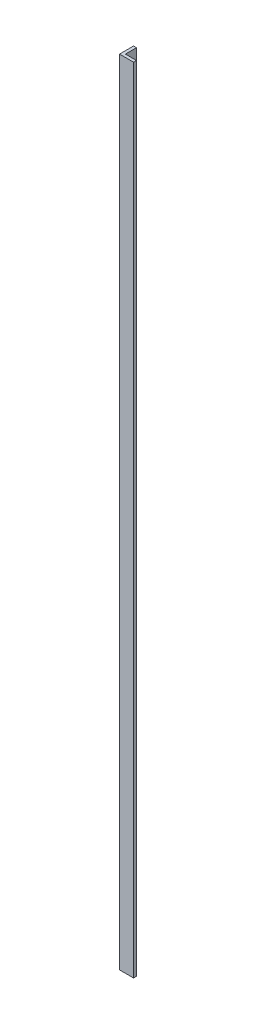
SolidWorks part; units mm, degrees
material "PE Low/Medium Density"
ref_plane "Front Plane" through (0, 0, 0) normal (0, 0, 1) x (1, 0, 0)
ref_plane "Top Plane" through (0, 0, 0) normal (0, 1, 0) x (1, 0, 0)
ref_plane "Right Plane" through (0, 0, 0) normal (1, 0, 0) x (0, 0, -1)
sketch "Sketch1" plane through (0, 0, 0) normal (0, 1, 0) x (1, 0, 0)
  line L1 (0, 0) -> (7.5875, 0)
  line L2 (0, 0) -> (0, 7.5875)
  line L3 (0, 7.5875) -> (1.5875, 7.5875)
  line L4 (7.5875, 0) -> (7.5875, 1.5875)
  line L7 (7.5875, 1.5875) -> (1.5875, 1.5875)
  line L8 (1.5875, 7.5875) -> (1.5875, 1.5875)
  dimension "D1" = 7.5875
  dimension "D2" = 7.5875
  dimension "D3" = 1.5875
  dimension "D4" = 1.5875
extrude "Boss-Extrude1" add sketch "Sketch1" along normal blind 429.9
